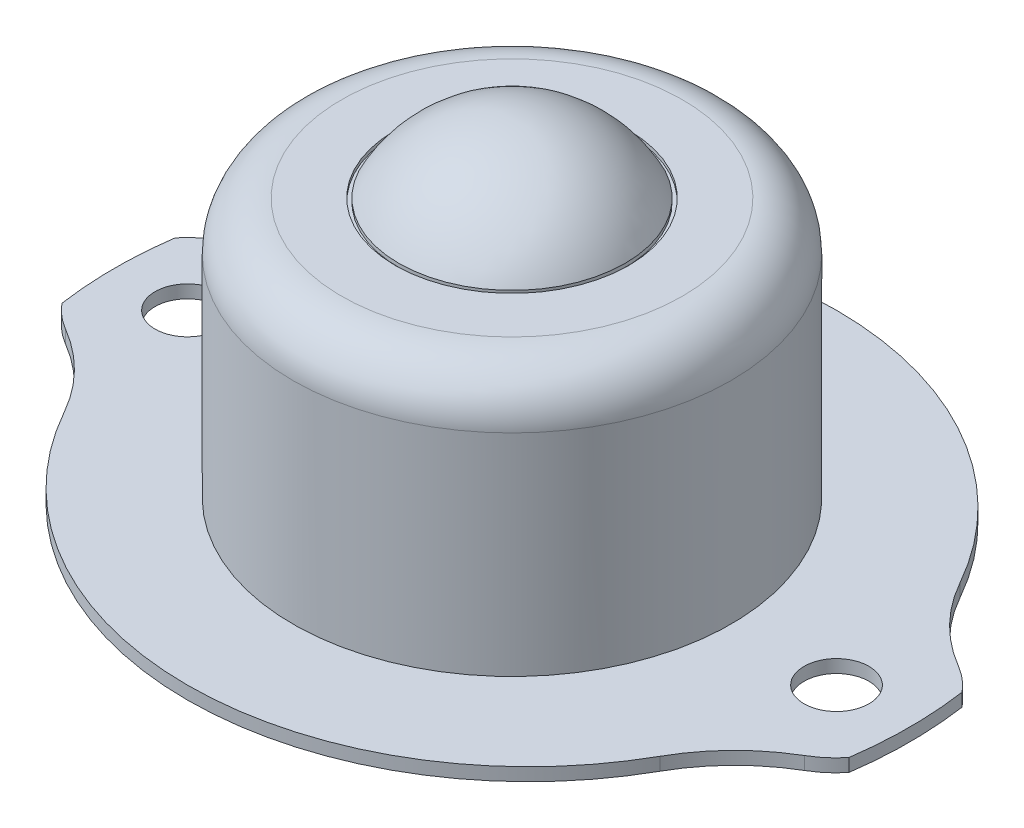
SolidWorks part; units mm, degrees
ref_plane "前视基准面" through (0, 0, 0) normal (0, 0, 1) x (1, 0, 0)
ref_plane "上视基准面" through (0, 0, 0) normal (0, 1, 0) x (1, 0, 0)
ref_plane "右视基准面" through (0, 0, 0) normal (1, 0, 0) x (0, 0, -1)
sketch "草图1" plane through (0, 0, 0) normal (0, 0, 1) x (1, 0, 0)
  line L0 (-6.98, 16.4) -> (13.5, 16.4)
  line L1 (0, 20.6) -> (0, -0.4)
  line L2 (-24.5, 0.4) -> (-13.5, 0.4)
  line L3 (-24.5, 0.4) -> (-24.5, -0.4)
  line L4 (-24.5, -0.4) -> (24.5, -0.4)
  line L5 (24.5, 0.4) -> (24.5, -0.4)
  line L7 (-7.2056, 16.4) -> (-7.2056, 16.1777)
  line L8 (-13.5, 16.4) -> (-7.2056, 16.4)
  line L9 (-13.5, 16.4) -> (-13.5, 0.4)
  line L11 (13.5, 16.4) -> (13.5, 0.4)
  line L17 (13.5, 0.4) -> (24.5, 0.4)
  line L18 (-7.2056, 16.1777) -> (-6.98, 16.1777)
  line L19 (-6.98, 16.4) -> (-6.98, 16.1777)
  arc A3 (6.98, 16.4) -> (-6.98, 16.4) centre (0, 12.7) ccw
  point P3 (0, 0)
  point P8 (0, 8.4)
  dimension "D1" = 49
  dimension "D2" = 0.8
  dimension "D3" = 27
  dimension "D5" = 16
  dimension "D7" = 13.1
revolve "旋转1" add sketch "草图1" angle 360 about L1 region at (-7.2076, 7.6994, 0)
revolve "旋转2" add sketch "草图1<3>" angle 360 about L1 region at (-2.7439, 18.1253, 0)
sketch "草图1<3>" plane through (0, 0, 0) normal (0, 0, 1) x (1, 0, 0) same geometry as "草图1"
fillet "圆角1" radius 3 1 edges at (-13.5, 16.4, 0)
sketch "草图2" plane through (0, -0.4, 0) normal (0, -1, 0) x (1, 0, 0)
  line L0 (-24.5, 0) -> (-13.5, 0) construction
  line L1 (13.5, 0) -> (24.5, 0) construction
  line L2 (-25.5, 0) -> (-18, 0) construction
  line L3 (18, 0) -> (25.5, 0) construction
  circle A0 centre (-20, 0) radius 2
  circle A1 centre (20, 0) radius 2
  circle A2 centre (0, 0) radius 25.5
  arc A3 (-22.7744, 4.749) -> (-22.7744, -4.749) centre (-20, 0) ccw
  arc A4 (22.7744, -4.749) -> (22.7744, 4.749) centre (20, 0) ccw
  arc A5 (-18.3575, 9.2471) -> (18.3575, 9.2471) centre (0, -1.0331) cw
  arc A6 (-18.3575, -9.2471) -> (18.3575, -9.2471) centre (0, 1.0331) ccw
  arc A7 (-18.3575, -9.2471) -> (-22.7744, -4.749) centre (-28.8276, -15.1104) ccw
  arc A8 (18.3575, -9.2471) -> (22.7744, -4.749) centre (28.8276, -15.1104) cw
  arc A9 (22.7744, 4.749) -> (18.3575, 9.2471) centre (28.8276, 15.1104) cw
  arc A10 (-18.3575, 9.2471) -> (-22.7744, 4.749) centre (-28.8276, 15.1104) cw
  point P23 (-20, -5.5)
  point P26 (20, -5.5)
  point P29 (20, 5.5)
  point P32 (-20, 5.5)
  circle M2 centre (0, 0) radius 24.5
  dimension "D1" = 40
  dimension "D3" = 4
  dimension "D4" = 4
  dimension "D5" = 12
  dimension "D2" = 20
extrude "切除-拉伸1" cut sketch "草图2" against normal blind 10 contours A10 A5 A9 A4 A2 A3 | A8 A6 A7 A3 A4 M2 | A0 | A1 region at (-20, -0.4, 0) region at (20, -0.4, 0) region at (0, -0.4, -23.9715) region at (23.9109, -0.4, 4.5878)
